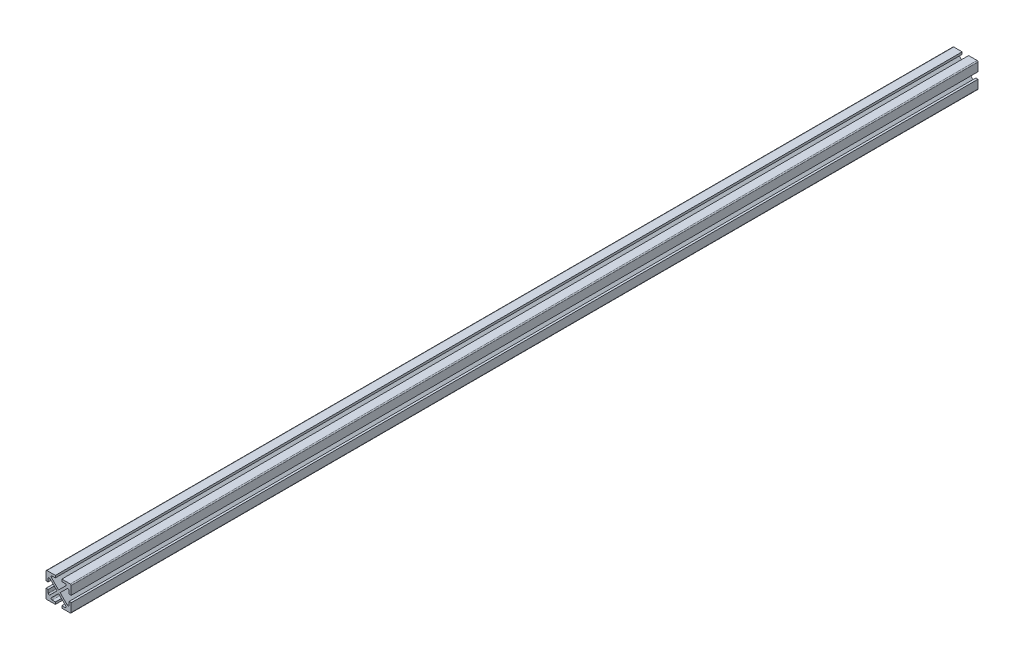
SolidWorks part; units mm, degrees
material "6061 Alloy"
ref_plane "Front Plane" through (0, 0, 0) normal (0, 0, 1) x (1, 0, 0)
ref_plane "Top Plane" through (0, 0, 0) normal (0, 1, 0) x (1, 0, 0)
ref_plane "Right Plane" through (0, 0, 0) normal (1, 0, 0) x (0, 0, -1)
sketch "Sketch1" plane through (0, 0, 0) normal (0, 0, 1) x (1, 0, 0)
  line L0 (-3.2512, 12.7) -> (-3.2512, 10.4902)
  line L9 (-12.7, -12.7) -> (12.7, -12.7)
  line L10 (-12.7, -12.7) -> (-12.7, 12.7)
  line L11 (-12.7, 12.7) -> (12.7, 12.7)
  line L12 (12.7, -12.7) -> (12.7, 12.7)
  line L13 (-12.7, -12.7) -> (12.7, 12.7) construction
  line L14 (-12.7, 12.7) -> (12.7, -12.7) construction
  line L17 (3.2512, 10.4902) -> (3.2512, 12.7)
  line L18 (0, 0) -> (0, 12.7) construction
  line L19 (-3.2512, 12.7) -> (3.2512, 12.7)
  line L20 (-8.9276, 10.4902) -> (0, 1.5626)
  line L21 (0, 1.5626) -> (8.9276, 10.4902)
  line L22 (8.9276, 10.4902) -> (3.2512, 10.4902)
  line L23 (-8.9276, 10.4902) -> (-3.2512, 10.4902)
  line L24 (10.4902, 8.9276) -> (10.4902, 3.2512)
  line L25 (12.7, 3.2512) -> (10.4902, 3.2512)
  line L26 (12.7, 3.2512) -> (12.7, -3.2512)
  line L27 (10.4902, -3.2512) -> (12.7, -3.2512)
  line L28 (10.4902, -8.9276) -> (10.4902, -3.2512)
  line L29 (1.5626, 0) -> (10.4902, -8.9276)
  line L30 (10.4902, 8.9276) -> (1.5626, 0)
  line L31 (8.9276, -10.4902) -> (3.2512, -10.4902)
  line L32 (3.2512, -12.7) -> (3.2512, -10.4902)
  line L33 (3.2512, -12.7) -> (-3.2512, -12.7)
  line L34 (-3.2512, -10.4902) -> (-3.2512, -12.7)
  line L35 (-8.9276, -10.4902) -> (-3.2512, -10.4902)
  line L36 (0, -1.5626) -> (-8.9276, -10.4902)
  line L37 (8.9276, -10.4902) -> (0, -1.5626)
  line L38 (-10.4902, -8.9276) -> (-10.4902, -3.2512)
  line L39 (-12.7, -3.2512) -> (-10.4902, -3.2512)
  line L40 (-12.7, -3.2512) -> (-12.7, 3.2512)
  line L41 (-10.4902, 3.2512) -> (-12.7, 3.2512)
  line L42 (-10.4902, 8.9276) -> (-10.4902, 3.2512)
  line L43 (-1.5626, 0) -> (-10.4902, 8.9276)
  line L44 (-10.4902, -8.9276) -> (-1.5626, 0)
  point P0 (0, 0)
  point P41 (0, 0)
  dimension "D1" = 25.4
  dimension "D2" = 6.5024
  dimension "D3" = 2.2098
  dimension "D4" = 2.2098
  dimension "D5" = 4
extrude "Boss-Extrude1" add sketch "Sketch1" along normal mid plane 914.4 contours L44 L38 L39 L10 L9 L34 L35 L36 L37 L31 L32 L12 L27 L28 L29 L30 L24 L25 L11 L17 L22 L21 L20 L23 L0 L41 L42 L43 region at (0, 0, 0)
fillet "Fillet1" radius 1 12 edges at (10.4902, 8.9276, 0) (8.9276, 10.4902, 0) (10.4902, -8.9276, 0) (8.9276, -10.4902, 0) (-8.9276, -10.4902, 0) (-10.4902, -8.9276, 0) (-10.4902, 8.9276, 0) (-8.9276, 10.4902, 0) (-12.7, -12.7, 0) (12.7, -12.7, 0) (12.7, 12.7, 0) (-12.7, 12.7, 0)
